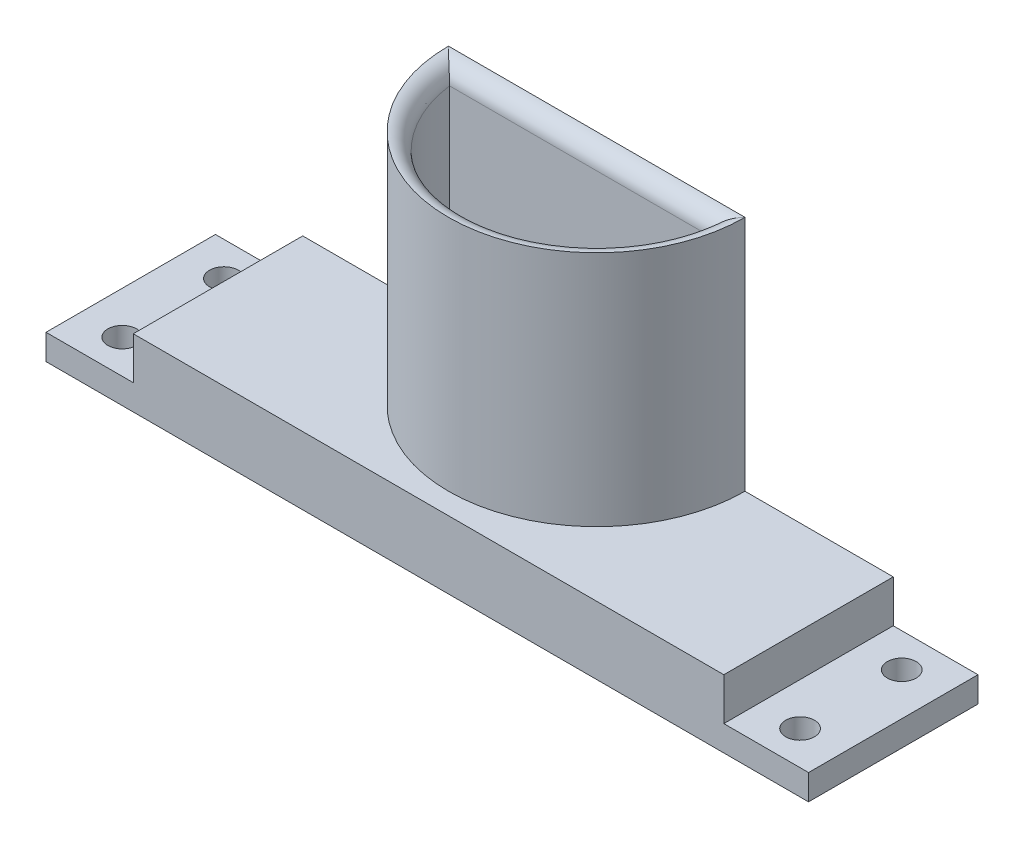
SolidWorks part; units mm, degrees
ref_plane "Front Plane" through (0, 0, 0) normal (0, 0, 1) x (1, 0, 0)
ref_plane "Top Plane" through (0, 0, 0) normal (0, 1, 0) x (1, 0, 0)
ref_plane "Right Plane" through (0, 0, 0) normal (1, 0, 0) x (0, 0, -1)
sketch "Sketch1" plane through (0, 0, 0) normal (0, 1, 0) x (1, 0, 0)
  line L1 (-35, -10) -> (35, -10)
  line L2 (-35, -10) -> (-35, 10)
  line L3 (-35, 10) -> (35, 10)
  line L4 (35, -10) -> (35, 10)
  line L5 (-35, -10) -> (35, 10) construction
  line L6 (-35, 10) -> (35, -10) construction
  point P0 (0, 0)
  dimension "D1" = 70
  dimension "D2" = 20
extrude "Boss-Extrude1" add sketch "Sketch1" along normal blind 5
sketch "Sketch2" plane through (0, 0, 0) normal (0, -1, 0) x (1, 0, 0)
  line L0 (-35, 10) -> (35, 10) construction
  line L1 (-45, -10) -> (45, -10)
  line L2 (-45, -10) -> (-45, 10)
  line L3 (-45, 10) -> (45, 10)
  line L4 (45, -10) -> (45, 10)
  line L5 (-45, -10) -> (45, 10) construction
  line L6 (-45, 10) -> (45, -10) construction
  point P0 (0, 0)
  dimension "D1" = 90
extrude "Boss-Extrude2" add sketch "Sketch2" along normal blind 3
sketch "Sketch3" plane through (0, 0, 0) normal (0, 1, 0) x (1, 0, 0)
  line L1 (-40.5, -15.25) -> (40.5, -15.25)
  line L2 (-40.5, -15.25) -> (-40.5, 15.25)
  line L3 (-40.5, 15.25) -> (40.5, 15.25)
  line L4 (40.5, -15.25) -> (40.5, 15.25)
  line L5 (-40.5, -15.25) -> (40.5, 15.25) construction
  line L6 (-40.5, 15.25) -> (40.5, -15.25) construction
  point P0 (0, 0)
  dimension "D1" = 30.5
  dimension "D2" = 81
sketch "Sketch4" plane through (0, 5, 0) normal (0, 1, 0) x (1, 0, 0)
  line L0 (35, 10) -> (-35, 10) construction
  line L1 (-17.5, 10) -> (17.5, 10)
  circle A0 centre (0, 10) radius 17.5
  line M2 (35, 10) -> (-35, 10)
  dimension "D1" = 35
extrude "Boss-Extrude3" add sketch "Sketch4" along normal blind 28 contours A0 M2 region at (0, 5, -2.5728)
sketch "Sketch6" plane through (0, 33, 0) normal (0, 1, 0) x (1, 0, 0)
  line L2 (15.3704, 8) -> (-15.3704, 8)
  line L3 (15.3704, 8) -> (-15.3704, 8)
  arc A2 (-15.3704, 8) -> (15.3704, 8) centre (0, 10) ccw
  arc A3 (-15.3704, 8) -> (15.3704, 8) centre (0, 10) ccw
  dimension "D1" = 2
extrude "Cut-Extrude1" cut sketch "Sketch6" against normal through all
fillet "Fillet1" radius 2 2 edges at (0, 33, 5.5) (0, 33, -8)
fillet "Fillet2" radius 2 2 edges at (0, -3, -8) (0, -3, 5.5)
hole_wizard "M3 Clearance Hole1" positions "Sketch7" profile "Sketch8" hole size "M3" standard "ANSI Metric"
sketch "Sketch7" plane through (0, 0, 0) normal (0, 1, 0) x (1, 0, 0)
  line L0 (-45, 10) -> (-35, 10) construction
  line L1 (35, 10) -> (45, 10) construction
  line L2 (45, -10) -> (35, -10) construction
  line L3 (-35, -10) -> (-45, -10) construction
  line L4 (-45, -10) -> (-45, 10) construction
  line L5 (45, 10) -> (45, -10) construction
  point P0 (-40, 6)
  point P2 (-40, -6)
  point P4 (40, 6)
  point P6 (40, -6)
  dimension "D1" = 4
  dimension "D2" = 4
  dimension "D3" = 4
  dimension "D4" = 4
  dimension "D5" = 5
  dimension "D6" = 5
sketch "Sketch8" plane through (-40, 0, -6) normal (1, 0, 0) x (0, 0, 1)
  line L0 (0, 0) -> (0, 11.0215)
  line L1 (0, 11.0215) -> (1.7, 10)
  line L2 (1.7, 10) -> (1.7, 0)
  line L5 (1.7, 0) -> (0, 0)
  line L10 (0, 11.0215) -> (-1.7, 10) construction
  line L11 (0, -6.35) -> (0, 107.95) construction
  dimension "Hole Dia." = 3.4
  dimension "Hole Depth" = 10
  dimension "Drill Angle" = 118
sketch "Sketch9" plane through (-35, 0, 0) normal (-1, 0, 0) x (0, 0, 1)
  line L4 (-10, 0) -> (10, 0)
  line L5 (10, 0) -> (10, 5)
  line L6 (10, 5) -> (-10, 5)
  line L7 (-10, 5) -> (-10, 0)
  line L8 (-10, 0) -> (10, 0)
  line L9 (10, 0) -> (10, 5)
  line L10 (10, 5) -> (-10, 5)
  line L11 (-10, 5) -> (-10, 0)
  dimension "D1" = 0
extrude "Cut-Extrude2" cut sketch "Sketch9" against normal blind 0.3
equation "\"8`\"=84.8464"
